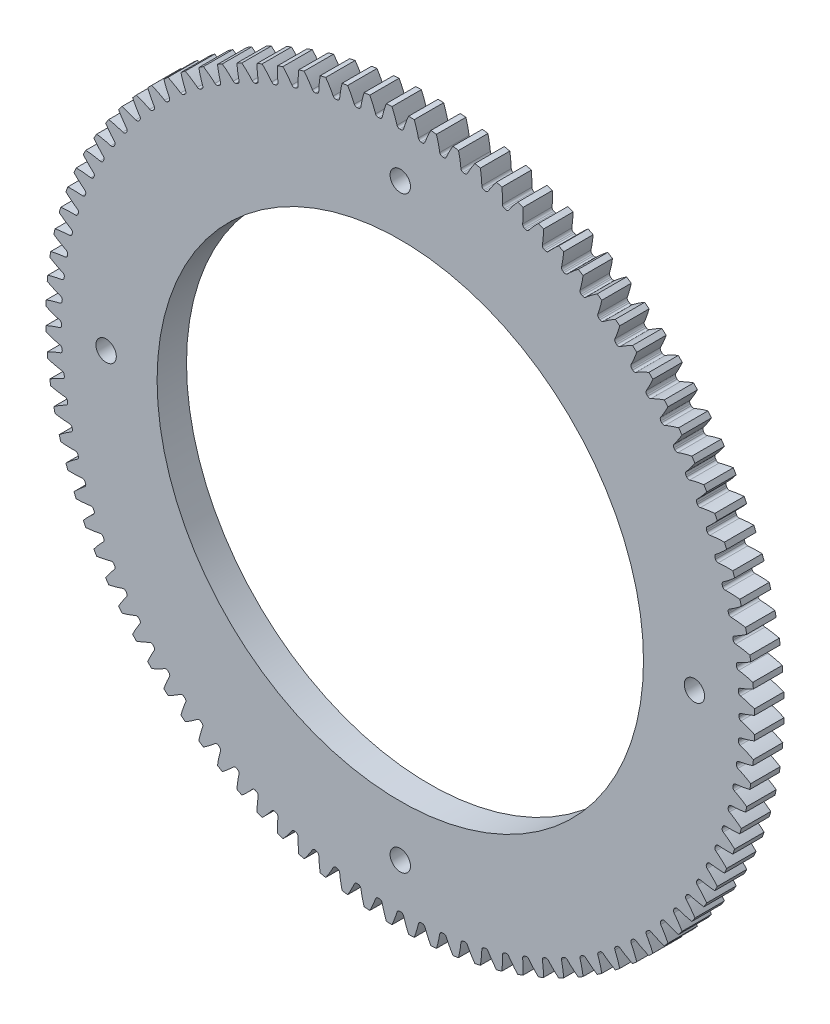
SolidWorks part; units mm, degrees
ref_plane "Front Plane" through (0, 0, 0) normal (0, 0, 1) x (1, 0, 0)
ref_plane "Top Plane" through (0, 0, 0) normal (0, 1, 0) x (1, 0, 0)
ref_plane "Right Plane" through (0, 0, 0) normal (1, 0, 0) x (0, 0, -1)
sketch "Sketch1" plane through (0, 0, 0) normal (0, 0, 1) x (1, 0, 0)
  line L0 (0, 0) -> (0, 75) construction
  line L1 (-24.1045, 83.7733) -> (24.1045, 66.2267) construction
  circle A0 centre (0, 0) radius 73.125 construction
  circle A1 centre (0, 0) radius 76.5 construction
  circle A2 centre (0, 0) radius 75 construction
  circle A3 centre (0, 0) radius 70.4769 construction
  circle A4 centre (0, 0) radius 40 construction
  circle A5 centre (0, 0) radius 7.5 construction
  point P8 (0.75, 0)
  point P13 (50, 0)
  dimension "OD" = 153
  dimension "Root Diameter" = 146.25
  dimension "Gear Pitch Diameter" = 150
  dimension "Base Diameter" = 140.9539
  dimension "Hub Diameter" = 80
  dimension "For Shaft Diameter" = 15
  dimension "Pressure Angle" = 20
  dimension "Number of Teeth" = 100
  dimension "Module" = 1.5
sketch "Sketch2" plane through (0, 0, 0) normal (1, 0, 0) x (0, 0, -1)
  line L0 (-14, 0) -> (6.35, 0) construction
  line L1 (6.35, 76.5) -> (6.35, -76.5) construction
  line L2 (0, -40) -> (-14, -40) construction
  line L3 (-14, 76.5) -> (6.35, 76.5) construction
  line L8 (-14, -40) -> (-14, 40) construction
  point P4 (0, 76.5)
  point P5 (-7, 0)
  dimension "Overall Width" = 20.35
  dimension "Hub Width" = 14
  dimension "Approx Set Screw Positon" = 7
  dimension "Face Width" = 6.35
sketch "Sketch3" plane through (0, 0, 0) normal (0, 0, 1) x (1, 0, 0)
  circle A0 centre (0, 0) radius 76.5
  circle A1 centre (0, 0) radius 76.5 construction
extrude "Boss-Extrude1" add sketch "Sketch3" against normal up to vertex (6.35 mm away) up to point (0, 0, -6.35)
sketch "Sketch4" plane through (0, 0, 0) normal (0, 0, 1) x (1, 0, 0)
  line L0 (73.1226, 0.589) -> (73.1226, -0.589)
  arc A3 (76.4789, 1.7978) -> (76.4789, -1.7978) centre (0, 0) cw
  circle A4 centre (0, 0) radius 76.5 construction
  arc A5 (73.1226, 0.589) -> (76.4789, 1.7978) centre (66.9977, 22.8603) ccw
  circle A8 centre (0, 0) radius 73.125 construction
  arc A9 (73.1226, -0.589) -> (76.4789, -1.7978) centre (66.9977, -22.8603) cw
  spline S0 degree 4 poles (70.4769, 0.0566) (70.4862, 0.0567) (70.5123, 0.0572) (70.5615, 0.0592) (70.6419, 0.0639) (70.7443, 0.072) (70.8767, 0.0848) (71.0327, 0.1031) (71.2042, 0.1265) (71.3909, 0.1556) (71.5772, 0.1877) (71.763, 0.2226) (71.9483, 0.2601) (72.1727, 0.3086) (72.4418, 0.3712) (72.7566, 0.4506) (73.1136, 0.5483) (73.4778, 0.6559) (73.8362, 0.7684) (74.1986, 0.8897) (74.5493, 1.0125) (74.9138, 1.148) (75.2504, 1.277) (75.6277, 1.4303) (75.9323, 1.5566) (76.3344, 1.7325) (76.572, 1.8392) (76.8501, 1.9673) (76.9736, 2.0258) (77.0497, 2.0619) knots 0 0 0 0 0 0.005377 0.015084 0.028532 0.04661 0.064855 0.092111 0.119476 0.146842 0.174209 0.201575 0.228941 0.256307 0.307035 0.361767 0.4165 0.471232 0.525964 0.580697 0.635429 0.690161 0.744894 0.799626 0.854358 0.909091 0.954545 1 1 1 1 1 construction
  spline S1 degree 4 poles (70.4769, 0.0566) (70.4862, 0.0567) (70.5123, 0.0572) (70.5615, 0.0592) (70.6419, 0.0639) (70.7443, 0.072) (70.8767, 0.0848) (71.0327, 0.1031) (71.2042, 0.1265) (71.3909, 0.1556) (71.5772, 0.1877) (71.763, 0.2226) (71.9483, 0.2601) (72.1727, 0.3086) (72.4418, 0.3712) (72.7566, 0.4506) (73.1136, 0.5483) (73.4778, 0.6559) (73.8362, 0.7684) (74.1986, 0.8897) (74.5493, 1.0125) (74.9138, 1.148) (75.2504, 1.277) (75.6277, 1.4303) (75.9323, 1.5566) (76.2472, 1.6943) (76.4005, 1.7625) (76.4789, 1.7978) knots 0 0 0 0 0 0.005377 0.015084 0.028532 0.04661 0.064855 0.092111 0.119476 0.146842 0.174209 0.201575 0.228941 0.256307 0.307035 0.361767 0.4165 0.471232 0.525964 0.580697 0.635429 0.690161 0.744894 0.799626 0.854358 0.909091 0.909091 0.909091 0.909091 0.909091 construction
  spline S2 degree 4 poles (70.4769, -0.0566) (70.4862, -0.0567) (70.5123, -0.0572) (70.5615, -0.0592) (70.6419, -0.0639) (70.7443, -0.072) (70.8767, -0.0848) (71.0327, -0.1031) (71.2042, -0.1265) (71.3909, -0.1556) (71.5772, -0.1877) (71.763, -0.2226) (71.9483, -0.2601) (72.1727, -0.3086) (72.4418, -0.3712) (72.7566, -0.4506) (73.1136, -0.5483) (73.4778, -0.6559) (73.8362, -0.7684) (74.1986, -0.8897) (74.5493, -1.0125) (74.9138, -1.148) (75.2504, -1.277) (75.6277, -1.4303) (75.9323, -1.5566) (76.3344, -1.7325) (76.572, -1.8392) (76.8501, -1.9673) (76.9736, -2.0258) (77.0497, -2.0619) knots 0 0 0 0 0 0.005377 0.015084 0.028532 0.04661 0.064855 0.092111 0.119476 0.146842 0.174209 0.201575 0.228941 0.256307 0.307035 0.361767 0.4165 0.471232 0.525964 0.580697 0.635429 0.690161 0.744894 0.799626 0.854358 0.909091 0.954545 1 1 1 1 1 construction
  spline S3 degree 4 poles (70.4769, -0.0566) (70.4862, -0.0567) (70.5123, -0.0572) (70.5615, -0.0592) (70.6419, -0.0639) (70.7443, -0.072) (70.8767, -0.0848) (71.0327, -0.1031) (71.2042, -0.1265) (71.3909, -0.1556) (71.5772, -0.1877) (71.763, -0.2226) (71.9483, -0.2601) (72.1727, -0.3086) (72.4418, -0.3712) (72.7566, -0.4506) (73.1136, -0.5483) (73.4778, -0.6559) (73.8362, -0.7684) (74.1986, -0.8897) (74.5493, -1.0125) (74.9138, -1.148) (75.2504, -1.277) (75.6277, -1.4303) (75.9323, -1.5566) (76.2472, -1.6943) (76.4005, -1.7625) (76.4789, -1.7978) knots 0 0 0 0 0 0.005377 0.015084 0.028532 0.04661 0.064855 0.092111 0.119476 0.146842 0.174209 0.201575 0.228941 0.256307 0.307035 0.361767 0.4165 0.471232 0.525964 0.580697 0.635429 0.690161 0.744894 0.799626 0.854358 0.909091 0.909091 0.909091 0.909091 0.909091 construction
  dimension "D1" = 1.1781
extrude "Cut-Extrude1" cut sketch "Sketch4" against normal through all both and the other way through all
fillet "Fillet1" radius 0.589 2 edges at (73.1226, 0.589, -3.175) (73.1226, -0.589, -3.175)
pattern_circular "CirPattern1" count 100 over 360 about axis through (0, 0, 14) along (0, 0, -1) of "Cut-Extrude1", "Fillet1"
sketch "Sketch5" plane through (0, 0, -6.35) normal (0, 0, -1) x (-1, 0, 0)
  circle A0 centre (0, 0) radius 52.5
  dimension "D1" = 105
extrude "Cut-Extrude2" cut sketch "Sketch5" against normal through all
sketch "Sketch6" plane through (0, 0, -6.35) normal (0, 0, -1) x (-1, 0, 0)
  circle A0 centre (63.5, 0) radius 2.2
  circle A1 centre (0, -63.5) radius 2.2
  circle A2 centre (-63.5, 0) radius 2.2
  circle A3 centre (0, 63.5) radius 2.2
  point P11 (0, 0)
  dimension "D1" = 4.4
  dimension "D3" = 127
  dimension "D2" = 4
extrude "Cut-Extrude3" cut sketch "Sketch6" against normal through all
sketch "Sketch7" plane through (0, 0, 0) normal (0, 0, 1) x (1, 0, 0)
  circle A0 centre (0, 0) radius 75 construction
  dimension "D1" = 150
sketch "Sketch8" plane through (0, 0, 0) normal (0, 1, 0) x (1, 0, 0)
  line L0 (0, 0) -> (0, 8.1709) construction
  line L1 (-75, 0) -> (75, 0) construction
equation "\"Number of Teeth\"= 100"
equation "\"Module\"= 1.5"
equation "\"Diametral Pitch\"= 1 / \"Module\""
equation "\"Dedendum\"= 1.25 / \"Diametral Pitch\""
equation "\"Pitch Diameter\"= \"Module\" * \"Number of Teeth\""
equation "\"Root Diameter\"= \"Pitch Diameter\" - ( 2 * \"Dedendum\" )"
equation "\"Root Diameter@Sketch1\"=\"Root Diameter\""
equation "\"OD@Sketch1\" = \"Outside Diameter\""
equation "\"D1@CirPattern1\"=\"Number of Teeth\""
equation "\"Pressure Angle\"=20"
equation "\"Base Diameter\"= \"Pitch Diameter\" * cos ( \"Pressure Angle\" )"
equation "\"Outside Diameter\"= ( \"Number of Teeth\" + 2 ) / \"Diametral Pitch\""
equation "\"Pitch Angle\"= 360deg / \"Number of Teeth\""
equation "\"Alpha\"= sqr ( \"Pitch Diameter\" ^ 2 - \"Base Diameter\" ^ 2 ) / \"Base Diameter\" * 180 / PI - \"Pressure Angle\""
equation "\"Beta\"= ( \"Pitch Angle\" / 4 - \"Alpha\" )"
equation "\"Phi\"= sqr ( ( \"Outside Diameter\" / 2 ) ^ 2 - ( \"Base Diameter\" / 2 ) ^ 2 ) / ( \"Base Diameter\" / 2 )"
equation "\"Addendum\"= 1 / \"Diametral Pitch\""
equation "\"WorkingDepth\"= 2 / \"Diametral Pitch\""
equation "\"WholeDepth\"= 2.25 / \"Diametral Pitch\""
equation "\"Clearance\"= 0.25 / \"Diametral Pitch\""
equation "\"ToothThickness\"= ( pi * 2 ) / \"Diametral Pitch\""
equation "\"CircularPitch\"= pi / \"Diametral Pitch\""
equation "\"Number of Teeth@Sketch1\"=\"Number of Teeth\""
equation "\"Module@Sketch1\"=\"Module\""
equation "\"Pressure Angle@Sketch1\"=\"Pressure Angle\""
equation "\"Gear Pitch Diameter@Sketch1\"=\"Pitch Diameter\""
equation "\"Base Diameter@Sketch1\"=\"Base Diameter\""
equation "\"Fillet\"= \"Clearance\" * cos ( \"Pressure Angle\" ) * tan ( ( 90 + \"Pressure Angle\" ) / 2 )"
equation "\"D1\"= \"Fillet\""
equation "\"Approx Set Screw Positon@Sketch2\" = \"Hub Width@Sketch2\" / 2"
equation "\"D2\"= \"Fillet\" * 2"
equation "\"D1@Sketch4\"=\"CircularPitch\"*0.25"
equation "\"D1@Fillet1\"=\"CircularPitch\"*0.125"
equation "\"Overall Width@Sketch2\"=14+0.25in"
equation "\"D3@Sketch6\"=5in"
